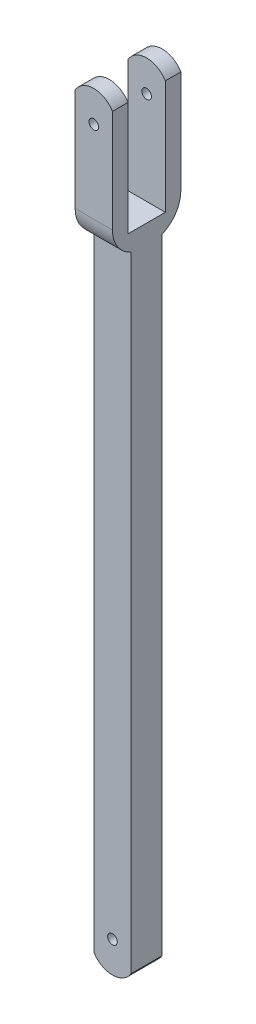
SolidWorks part; units mm, degrees
ref_plane "Front Plane" through (0, 0, 0) normal (0, 0, 1) x (1, 0, 0)
ref_plane "Top Plane" through (0, 0, 0) normal (0, 1, 0) x (1, 0, 0)
ref_plane "Right Plane" through (0, 0, 0) normal (1, 0, 0) x (0, 0, -1)
sketch "Esquisse1" plane through (0, 0, 0) normal (0, 0, 1) x (1, 0, 0)
  line L2 (-6.8285, -151.713) -> (-6.8285, 91.4981)
  line L4 (5.1715, -151.713) -> (5.1715, 91.4981)
  arc A0 (5.1715, 91.4981) -> (-6.8285, 91.4981) centre (-0.8285, 87.8925) ccw
  arc A1 (-6.8285, -151.713) -> (5.1715, -151.713) centre (-0.8285, -148.1075) ccw
  point P0 (0, 0)
  point P1 (-0.8285, -155.1075)
  point P3 (-0.8285, 94.8925)
  dimension "D3" = 14
  dimension "D4" = 14
  dimension "D1" = 250
  dimension "D2" = 12
extrude "Boss.-Extru.1" add sketch "Esquisse1" along normal blind 11 and the other way blind 11
ref_plane "Plane1" through (0, 94.8925, 0) normal (0, 1, 0) x (1, 0, 0)
sketch "Esquisse3" plane through (0, 94.8925, 0) normal (0, 1, 0) x (1, 0, 0)
  line L7 (-7, 0) -> (49993, 0) construction
  line L13 (-8.0887, -6) -> (8.4927, -6)
  line L14 (-8.0887, -6) -> (-8.0887, 6)
  line L15 (-8.0887, 6) -> (8.4927, 6)
  line L17 (8.4927, -6) -> (8.4927, 6)
  line L18 (-8.0887, -6) -> (8.4927, 6) construction
  line L19 (-8.0887, 6) -> (8.4927, -6) construction
  line L20 (5.1715, 11) -> (-6.8285, 11) construction
  line L21 (-6.8285, -11) -> (5.1715, -11) construction
  point P5 (0.202, 0)
  dimension "D1" = 5
  dimension "D2" = 5
extrude "Enlèv. mat.-Extru.2" cut sketch "Esquisse3" against normal blind 40
sketch "Sketch1" plane through (0, 0, 11) normal (0, 0, 1) x (1, 0, 0)
  line L1 (-0.8285, 90.5285) -> (-0.8285, -49909.4715) construction
  line L2 (-6.8285, 91.4981) -> (-6.8285, -151.713) construction
  line L3 (5.1715, -151.713) -> (5.1715, 91.4981) construction
  circle A0 centre (-0.8285, 84.8904) radius 1.55
  circle A1 centre (-0.8285, -145.1075) radius 1.55
  arc A6 (5.1715, 91.4981) -> (-6.8285, 91.4981) centre (-0.8285, 87.8925) ccw construction
  arc A7 (-6.8285, -151.713) -> (5.1715, -151.713) centre (-0.8285, -148.1075) ccw construction
  point P10 (0, 0)
  point P11 (-0.8285, 94.8925)
  point P16 (-0.8285, -155.1075)
  dimension "D1" = 3.1
  dimension "D2" = 10.0021
  dimension "D3" = 3.1
  dimension "D4" = 10
extrude "Cut-Extrude1" cut sketch "Sketch1" against normal up to surface (22 mm away) up to face at (-0.8285, -30.1075, -11)
sketch "Sketch4" plane through (0, 0, 11) normal (0, 0, 1) x (1, 0, 0)
  line L0 (-6.8285, 49.2783) -> (-6.8285, -151.713)
  line L1 (-6.8285, 91.4981) -> (-6.8285, -151.713) construction
  line L2 (-6.8285, 49.2783) -> (5.1715, 49.2783)
  line L3 (5.1715, -151.713) -> (5.1715, 91.4981) construction
  line L4 (5.1715, 49.2783) -> (5.1715, -151.713)
  arc A0 (-6.8285, -151.713) -> (5.1715, -151.713) centre (-0.8285, -151.713) ccw
  arc A1 (-6.8285, -151.713) -> (5.1715, -151.713) centre (-0.8285, -148.1075) ccw construction
extrude "Cut-Extrude2" cut sketch "Sketch4" against normal blind 6
mirror "Mirror1" about plane through (0, 0, 0) normal (0, 0, 1) of "Cut-Extrude2"
fillet "Fillet1" radius 10 2 edges at (-0.8285, 49.2783, -11) (-0.8285, 49.2783, 11)
equation "\"ScrewSize\"= 3.1mm"
